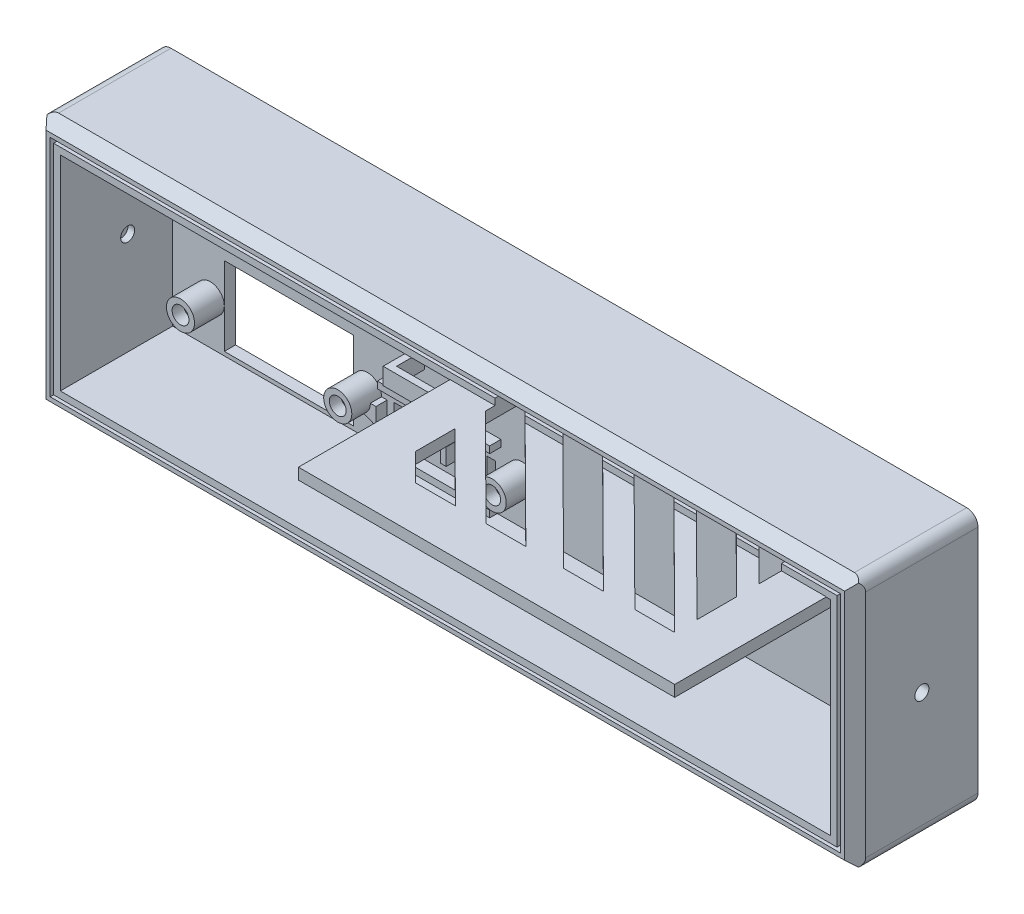
SolidWorks part; units mm, degrees
ref_plane "Front Plane" through (0, 0, 0) normal (0, 0, 1) x (1, 0, 0)
ref_plane "Top Plane" through (0, 0, 0) normal (0, 1, 0) x (1, 0, 0)
ref_plane "Right Plane" through (0, 0, 0) normal (1, 0, 0) x (0, 0, -1)
sketch "Sketch1" plane through (0, 0, 0) normal (0, 0, 1) x (1, 0, 0)
  line L1 (0, 0) -> (145.7, 0)
  line L2 (0, 0) -> (0, 45)
  line L3 (0, 45) -> (145.7, 45)
  line L4 (145.7, 0) -> (145.7, 45)
  dimension "D1" = 45
  dimension "D2" = 145.7
extrude "Boss-Extrude1" add sketch "Sketch1" along normal blind 2
sketch "Sketch2" plane through (0, 0, 0) normal (0, 0, -1) x (-1, 0, 0)
  line L0 (0, 45) -> (0, 0) construction
  line L1 (-30, 32.1) -> (-45, 32.1)
  line L2 (-30, 32.1) -> (-30, 39)
  line L3 (-30, 39) -> (-45, 39)
  line L4 (-45, 32.1) -> (-45, 39)
  line L5 (-50, 32.1) -> (-65, 32.1)
  line L6 (-50, 32.1) -> (-50, 39)
  line L7 (-50, 39) -> (-65, 39)
  line L8 (-65, 32.1) -> (-65, 39)
  line L9 (-145.7, 45) -> (0, 45) construction
  dimension "D1" = 6.9
  dimension "D2" = 15
  dimension "D3" = 5
  dimension "D4" = 30
  dimension "D5" = 6
extrude "usb" cut sketch "Sketch2" against normal up to next
sketch "Sketch3" plane through (0, 0, 2) normal (0, 0, 1) x (1, 0, 0)
  line L0 (65, 32.1) -> (65, 39) construction
  line L1 (45, 30.6) -> (30, 30.6)
  line L2 (45, 30.6) -> (45, 39)
  line L3 (45, 39) -> (30, 39)
  line L4 (30, 30.6) -> (30, 39)
  line L5 (50, 30.6) -> (65, 30.6)
  line L6 (50, 30.6) -> (50, 39)
  line L7 (50, 39) -> (65, 39)
  line L8 (65, 30.6) -> (65, 39)
  line L9 (30, 39) -> (30, 32.1) construction
  line L10 (45, 39) -> (30, 39) construction
  dimension "D1" = 8.4
extrude "usb_back" cut sketch "Sketch3" against normal blind 1
sketch "Sketch4" plane through (0, 0, 2) normal (0, 0, 1) x (1, 0, 0)
  line L0 (65, 39) -> (65, 37)
  line L5 (45, 39) -> (45, 37)
  line L10 (45, 30.6) -> (45, 39) construction
  line L15 (45, 37) -> (46.2, 37)
  line L24 (46.2, 37) -> (46.2, 41)
  line L25 (46.2, 41) -> (28.8, 41)
  line L26 (28.8, 41) -> (28.8, 37)
  line L27 (65, 30.6) -> (65, 39) construction
  line L28 (65, 37) -> (66.2, 37)
  line L29 (66.2, 37) -> (66.2, 41)
  line L30 (66.2, 41) -> (48.8, 41)
  line L31 (48.8, 41) -> (48.8, 37)
  line L32 (48.8, 37) -> (50, 37)
  line L33 (50, 39) -> (50, 30.6) construction
  line L34 (50, 37) -> (50, 39)
  line L35 (50, 39) -> (65, 39)
  line L44 (28.8, 37) -> (30, 37)
  line L45 (30, 39) -> (30, 30.6) construction
  line L46 (30, 37) -> (30, 39)
  line L47 (45, 39) -> (30, 39) construction
  line L48 (30, 39) -> (45, 39)
  dimension "D1" = 1.2
  dimension "D2" = 2
  dimension "D3" = 4
extrude "usb_back_support" add sketch "Sketch4" along normal blind 8
sketch "Sketch5" plane through (0, 0, 10) normal (0, 0, 1) x (1, 0, 0)
  line L1 (28.8, 37) -> (46.2, 37)
  line L2 (28.8, 37) -> (28.8, 41)
  line L3 (28.8, 41) -> (46.2, 41)
  line L4 (46.2, 37) -> (46.2, 41)
  line L5 (48.8, 37) -> (66.2, 37)
  line L6 (48.8, 37) -> (48.8, 41)
  line L7 (48.8, 41) -> (66.2, 41)
  line L8 (66.2, 37) -> (66.2, 41)
  line L10 (46.2, 41) -> (28.8, 41) construction
  line L11 (66.2, 41) -> (48.8, 41) construction
extrude "usb_back_support_2" add sketch "Sketch5" along normal blind 1.5
sketch "Sketch6" plane through (0, 0, 0) normal (0, 0, -1) x (-1, 0, 0)
  line L0 (0, 45) -> (0, 0) construction
  line L1 (-13.5, 5) -> (-36.5, 5)
  line L2 (-13.5, 5) -> (-13.5, 19)
  line L3 (-13.5, 19) -> (-36.5, 19)
  line L4 (-36.5, 5) -> (-36.5, 19)
  line L9 (0, 0) -> (-145.7, 0) construction
  dimension "D1" = 23
  dimension "D2" = 14
  dimension "D4" = 13.5
  dimension "D5" = 5
extrude "voltmeter_hole" cut sketch "Sketch6" against normal up to next
sketch "Sketch7" plane through (0, 0, 2) normal (0, 0, 1) x (1, 0, 0)
  line L0 (36.5, 19) -> (36.5, 5) construction
  line L1 (36.5, 5) -> (36.5, 19) construction
  line L3 (13.5, 19) -> (13.5, 5) construction
  circle A0 centre (66.5, 12) radius 2.5
  circle A1 centre (39, 12) radius 2.5
  circle A2 centre (11, 12) radius 2.5
  point P9 (36.5, 12)
  dimension "D1" = 2.5
  dimension "D2" = 5
  dimension "D3" = 2.5
  dimension "D4" = 30
extrude "voltmeter_plot" add sketch "Sketch7" along normal blind 5.3
sketch "Sketch10" plane through (0, 0, 7.3) normal (0, 0, 1) x (1, 0, 0)
  circle A0 centre (66.5, 12) radius 1.5
  circle A1 centre (39, 12) radius 1.5
  circle A2 centre (11, 12) radius 1.5
  circle A3 centre (11, 12) radius 2.5 construction
  circle A4 centre (39, 12) radius 2.5 construction
  circle A5 centre (66.5, 12) radius 2.5 construction
  dimension "D1" = 3
extrude "plot_hole" cut sketch "Sketch10" against normal blind 2
sketch "Sketch8" plane through (0, 0, 2) normal (0, 0, 1) x (1, 0, 0)
  line L0 (145.7, 45) -> (0, 45) construction
  line L1 (140.7, 38.75) -> (73.7, 38.75)
  line L2 (140.7, 38.75) -> (140.7, 40.75)
  line L3 (140.7, 40.75) -> (73.7, 40.75)
  line L4 (73.7, 38.75) -> (73.7, 40.75)
  line L5 (145.7, 0) -> (145.7, 45) construction
  dimension "D1" = 2
  dimension "D2" = 67
  dimension "D3" = 4.25
  dimension "D4" = 5
extrude "Boss-Extrude5" add sketch "Sketch8" along normal blind 47
sketch "Sketch9" plane through (0, 0, 0) normal (0, 0, -1) x (-1, 0, 0)
  line L0 (-30, 32.1) -> (-30, 39) construction
  line L1 (-20, 31) -> (-27, 31)
  line L2 (-20, 31) -> (-20, 40.5)
  line L3 (-20, 40.5) -> (-27, 40.5)
  line L4 (-27, 31) -> (-27, 40.5)
  line L5 (-8, 29.5) -> (-17, 29.5)
  line L6 (-8, 29.5) -> (-8, 40.5)
  line L7 (-8, 40.5) -> (-17, 40.5)
  line L8 (-17, 29.5) -> (-17, 40.5)
  line L9 (-145.7, 45) -> (0, 45) construction
  dimension "D1" = 7
  dimension "D2" = 9.5
  dimension "D3" = 3
  dimension "D4" = 4.5
  dimension "D5" = 9
  dimension "D6" = 11
  dimension "D7" = 3
extrude "dc" cut sketch "Sketch9" against normal up to next
sketch "Sketch11" plane through (0, 0, 0) normal (0, 0, -1) x (-1, 0, 0)
  line L0 (-36.5, 19) -> (-36.5, 5) construction
  line L1 (-43.75, 8.75) -> (-45.25, 8.75)
  line L2 (-43.75, 8.75) -> (-43.75, 12.25)
  line L3 (-43.75, 12.25) -> (-45.25, 12.25)
  line L4 (-45.25, 8.75) -> (-45.25, 12.25)
  line L5 (-47.75, 8.75) -> (-49.25, 8.75)
  line L6 (-47.75, 8.75) -> (-47.75, 12.25)
  line L7 (-47.75, 12.25) -> (-49.25, 12.25)
  line L8 (-49.25, 8.75) -> (-49.25, 12.25)
  line L9 (-56.25, 8.75) -> (-57.75, 8.75)
  line L10 (-56.25, 8.75) -> (-56.25, 12.25)
  line L11 (-56.25, 12.25) -> (-57.75, 12.25)
  line L12 (-57.75, 8.75) -> (-57.75, 12.25)
  line L13 (-60.25, 8.75) -> (-61.75, 8.75)
  line L14 (-60.25, 8.75) -> (-60.25, 12.25)
  line L15 (-60.25, 12.25) -> (-61.75, 12.25)
  line L16 (-61.75, 8.75) -> (-61.75, 12.25)
  circle A0 centre (-39, 12) radius 2.5 construction
  point P16 (-43.75, 10.5)
  dimension "D1" = 1.5
  dimension "D2" = 3.5
  dimension "D3" = 7.25
  dimension "D4" = 2.5
  dimension "D5" = 7
  dimension "D6" = 2.5
  dimension "D7" = 1.5
extrude "switch_hola" cut sketch "Sketch11" against normal up to next
sketch "Sketch12" plane through (0, 0, 2) normal (0, 0, 1) x (1, 0, 0)
  line L0 (62.75, 14.85) -> (42.75, 14.85)
  line L3 (65.25, 12) -> (63, 12)
  line L4 (63, 9) -> (63, 12)
  line L9 (55, 9) -> (54, 9)
  line L10 (55, 9) -> (55, 12)
  line L11 (55, 12) -> (54, 12)
  line L12 (54, 9) -> (54, 12)
  line L13 (51.5, 9) -> (50.5, 9)
  line L14 (51.5, 9) -> (51.5, 12)
  line L15 (51.5, 12) -> (50.5, 12)
  line L16 (50.5, 9) -> (50.5, 12)
  line L22 (42.5, 9) -> (42.5, 12)
  line L23 (42.5, 12) -> (40.25, 12)
  line L49 (62.75, 4.95) -> (42.75, 4.95)
  line L50 (62.75, 4.95) -> (62.75, 6.15)
  line L51 (62.75, 6.15) -> (42.75, 6.15)
  line L52 (42.75, 4.95) -> (42.75, 6.15)
  line L57 (62.75, 14.85) -> (62.75, 16.05)
  line L58 (62.75, 16.05) -> (42.75, 16.05)
  line L59 (42.75, 14.85) -> (42.75, 16.05)
  line L60 (61.75, 10.5) -> (43.75, 10.5) construction
  line L61 (61.75, 8.75) -> (61.75, 12.25) construction
  line L62 (43.75, 12.25) -> (43.75, 8.75) construction
  line L63 (44.5, 12.25) -> (44.5, 8.75) construction
  line L64 (45.25, 12.25) -> (43.75, 12.25) construction
  line L65 (43.75, 8.75) -> (45.25, 8.75) construction
  line L66 (48.5, 12.25) -> (48.5, 8.75) construction
  line L67 (49.25, 12.25) -> (47.75, 12.25) construction
  line L68 (47.75, 8.75) -> (49.25, 8.75) construction
  line L69 (57, 12.25) -> (57, 8.75) construction
  line L70 (57.75, 12.25) -> (56.25, 12.25) construction
  line L71 (56.25, 8.75) -> (57.75, 8.75) construction
  line L72 (61, 12.25) -> (61, 8.75) construction
  line L73 (61.75, 12.25) -> (60.25, 12.25) construction
  line L74 (60.25, 8.75) -> (61.75, 8.75) construction
  line L75 (40.25, 12) -> (40.25, 9.8349)
  line L76 (40.25, 9.8349) -> (42.5, 9)
  line L77 (65.25, 12) -> (65.25, 9.8349)
  line L78 (65.25, 9.8349) -> (63, 9)
  circle A0 centre (66.5, 12) radius 2.5 construction
  circle A1 centre (39, 12) radius 2.5 construction
  point P54 (42.5, 10.5)
  point P55 (55, 10.5)
  point P56 (50.5, 10.5)
  point P58 (52.75, 10.5)
  point P59 (52.75, 14.85)
  dimension "D3" = 8.7
  dimension "D8" = 2
  dimension "D1" = 20
  dimension "D2" = 1.2
  dimension "D4" = 2.25
  dimension "D5" = 2
  dimension "D6" = 3
  dimension "D7" = 2
  dimension "D10" = 1
  dimension "D9" = 2
  dimension "D11" = 1
extrude "switch_block" add sketch "Sketch12" along normal blind 2
sketch "Sketch13" plane through (0, 0, 2) normal (0, 0, 1) x (1, 0, 0)
  line L0 (62.75, 16.05) -> (42.75, 16.05) construction
  line L1 (47.9765, 23.05) -> (49.1765, 23.05)
  line L2 (47.9765, 23.05) -> (47.9765, 20.05)
  line L3 (47.9765, 20.05) -> (49.1765, 20.05)
  line L4 (49.1765, 23.05) -> (49.1765, 20.05)
  line L5 (59.1765, 23.05) -> (60.3765, 23.05)
  line L6 (59.1765, 23.05) -> (59.1765, 20.05)
  line L7 (59.1765, 20.05) -> (60.3765, 20.05)
  line L8 (60.3765, 23.05) -> (60.3765, 20.05)
  dimension "D1" = 1.2
  dimension "D2" = 3
  dimension "D3" = 4
  dimension "D4" = 10
extrude "support potar" add sketch "Sketch13" along normal blind 5
sketch "Sketch14" plane through (0, 0, 7) normal (0, 0, 1) x (1, 0, 0)
  line L1 (47.9765, 23.05) -> (60.3765, 23.05)
  line L2 (47.9765, 23.05) -> (47.9765, 20.05)
  line L3 (47.9765, 20.05) -> (60.3765, 20.05)
  line L4 (60.3765, 23.05) -> (60.3765, 20.05)
extrude "Boss-Extrude7" add sketch "Sketch14" along normal blind 1.2
sketch "Sketch15" plane through (0, 0, 2) normal (0, 0, 1) x (1, 0, 0)
  line L1 (46.8265, 29.6) -> (54.3265, 29.6)
  line L2 (46.8265, 29.6) -> (46.8265, 27.6)
  line L3 (46.8265, 27.6) -> (54.3265, 27.6)
  line L4 (54.3265, 29.6) -> (54.3265, 27.6)
  line L5 (50, 30.6) -> (65, 30.6) construction
  line L7 (59.1765, 23.05) -> (59.1765, 20.05) construction
  point P6 (50.5765, 27.6)
  dimension "D1" = 2
  dimension "D2" = 7.5
  dimension "D3" = 1
  dimension "D4" = 8.6
extrude "trou roulette" cut sketch "Sketch15" against normal up to next
sketch "Sketch16" plane through (0, 0, 2) normal (0, 0, 1) x (1, 0, 0)
  line L0 (54.3265, 29.6) -> (46.8265, 29.6) construction
  line L1 (54.8265, 29.6) -> (46.3265, 29.6)
  line L2 (54.8265, 29.6) -> (54.8265, 27.6)
  line L3 (54.8265, 27.6) -> (46.3265, 27.6)
  line L4 (46.3265, 29.6) -> (46.3265, 27.6)
  line L5 (46.8265, 27.6) -> (54.3265, 27.6) construction
  point P8 (50.5765, 29.6)
  point P9 (50.5765, 29.6)
  dimension "D1" = 8.5
extrude "Cut-Extrude2" cut sketch "Sketch16" against normal blind 0.5
sketch "Sketch17" plane through (0, 0, 2) normal (0, 0, 1) x (1, 0, 0)
  line L1 (0, 45) -> (145.7, 45)
  line L2 (0, 45) -> (0, 0)
  line L3 (0, 0) -> (145.7, 0)
  line L4 (145.7, 45) -> (145.7, 0)
  line L5 (143.2, 2.5) -> (2.5, 2.5)
  line L6 (143.2, 2.5) -> (143.2, 42.5)
  line L7 (143.2, 42.5) -> (2.5, 42.5)
  line L8 (2.5, 2.5) -> (2.5, 42.5)
  line L9 (3.1, 41.9) -> (142.6, 41.9)
  line L10 (3.1, 41.9) -> (3.1, 3.1)
  line L11 (3.1, 3.1) -> (142.6, 3.1)
  line L12 (142.6, 41.9) -> (142.6, 3.1)
  line L13 (4.3, 40.7) -> (141.4, 40.7)
  line L14 (4.3, 40.7) -> (4.3, 4.3)
  line L15 (4.3, 4.3) -> (141.4, 4.3)
  line L16 (141.4, 40.7) -> (141.4, 4.3)
  point P18 (143.2, 22.5)
  point P19 (145.7, 22.5)
  point P20 (142.6, 22.5)
  point P21 (141.4, 22.5)
  point P22 (72.85, 42.5)
  point P23 (72.85, 45)
  point P24 (72.85, 41.9)
  point P25 (72.85, 40.7)
  dimension "D1" = 0.6
  dimension "D2" = 0.6
  dimension "D3" = 2.5
  dimension "D4" = 2.5
  dimension "D5" = 1.2
  dimension "D6" = 1.2
extrude "bord " add sketch "Sketch17" along normal blind 20 contours L4 L1 L2 L3 L5 L8 L7 L6 | L12 L9 L10 L11 L13 L16 L15 L14 region at (72.85, 43.4751, 2) region at (72.85, 41.7552, 2)
fillet "Fillet1" radius 2 4 edges at (0, 0, 11) (145.7, 0, 11) (145.7, 45, 11) (0, 45, 11)
sketch "Sketch18" plane through (0, 38.75, 0) normal (0, -1, 0) x (1, 0, 0)
  line L0 (81.7, 36.1785) -> (86.5549, 41)
  line L1 (86.5549, 41) -> (93.6505, 41)
  line L2 (93.6505, 41) -> (81.7, 29.1318)
  line L3 (81.7, 29.1318) -> (81.7, 36.1785)
  line L4 (81.7, 23.7224) -> (99.0973, 41)
  line L5 (99.0973, 41) -> (106.1929, 41)
  line L6 (106.1929, 41) -> (81.7, 16.6757)
  line L7 (81.7, 16.6757) -> (81.7, 23.7224)
  line L8 (81.7, 10) -> (112.9148, 41)
  line L9 (112.9148, 41) -> (120.0104, 41)
  line L10 (120.0104, 41) -> (88.7956, 10)
  line L11 (88.7956, 10) -> (81.7, 10)
  line L12 (140.7, 49) -> (140.7, 2) construction
  line L13 (94.3896, 10) -> (125.6044, 41)
  line L14 (125.6044, 41) -> (132.7, 41)
  line L15 (132.7, 41) -> (101.4852, 10)
  line L16 (101.4852, 10) -> (94.3896, 10)
  line L17 (105.4795, 10) -> (132.7, 37.0331)
  line L18 (132.7, 37.0331) -> (132.7, 29.9864)
  line L19 (132.7, 29.9864) -> (112.5751, 10)
  line L20 (112.5751, 10) -> (105.4795, 10)
  line L21 (116.6029, 10) -> (132.7, 25.9864)
  line L22 (132.7, 25.9864) -> (132.7, 18.9396)
  line L23 (132.7, 18.9396) -> (123.6985, 10)
  line L24 (123.6985, 10) -> (116.6029, 10)
  line L25 (73.7, 49) -> (140.7, 49) construction
  line L26 (73.7, 2) -> (140.7, 2) construction
  line L27 (73.7, 49) -> (73.7, 2) construction
  dimension "D1" = 5
  dimension "D2" = 8
  dimension "D3" = 8
  dimension "D4" = 8
  dimension "D5" = 8
  dimension "D6" = 4
extrude "Cut-Extrude3" cut sketch "Sketch18" against normal up to surface (3.15 mm away) up to face at (72.85, 41.9, 12)
sketch "Sketch19" plane through (145.7, 0, 0) normal (1, 0, 0) x (0, 0, -1)
  line L0 (-22, 43.25) -> (-20, 45)
  line L1 (-22, 43) -> (-22, 2) construction
  line L2 (-20, 45) -> (-22, 45)
  line L3 (-22, 45) -> (-22, 43.25)
  line L4 (-22, 45) -> (0, 45) construction
  line L5 (-22, 1.75) -> (-20, 0)
  line L6 (0, 0) -> (-22, 0) construction
  line L7 (-20, 0) -> (-22, 0)
  line L8 (-22, 0) -> (-22, 1.75)
  dimension "D1" = 2
  dimension "D2" = 1.75
extrude "Cut-Extrude4" cut sketch "Sketch19" against normal up to surface (145.7 mm away) up to face at (0, 22.5, 11)
sketch "Sketch20" plane through (0, 0, 0) normal (0, -1, 0) x (-1, 0, 0)
  line L0 (-143.95, -22) -> (-145.7, -20)
  line L1 (-0.0157, -22) -> (-145.6843, -22) construction
  line L3 (-145.7, -20) -> (-145.7, -22)
  line L4 (-145.7, -22) -> (-143.95, -22)
  line L5 (-1.75, -22) -> (0, -20)
  line L7 (0, -20) -> (0, -22)
  line L8 (0, -22) -> (-1.75, -22)
  line L9 (-145.7, 0) -> (-145.7, -22) construction
  line L10 (0, -22) -> (0, 0) construction
  dimension "D1" = 1.75
  dimension "D2" = 2
extrude "Cut-Extrude5" cut sketch "Sketch20" against normal up to surface (45 mm away) up to face at (72.85, 45, 10)
sketch "Sketch21" plane through (0, 0, 0) normal (-1, 0, 0) x (0, 0, 1)
  line L0 (20, 43) -> (20, 2) construction
  line L1 (0, 2) -> (20, 2) construction
  circle A0 centre (10, 22.5) radius 1.25
  point P2 (0, 0)
  point P5 (20, 22.5)
  point P6 (0, 0)
  point P9 (10, 2)
  dimension "D1" = 2.5
extrude "Cut-Extrude6" cut sketch "Sketch21" against normal up to surface (145.7 mm away) up to face at (145.7, 22.5, 10)
